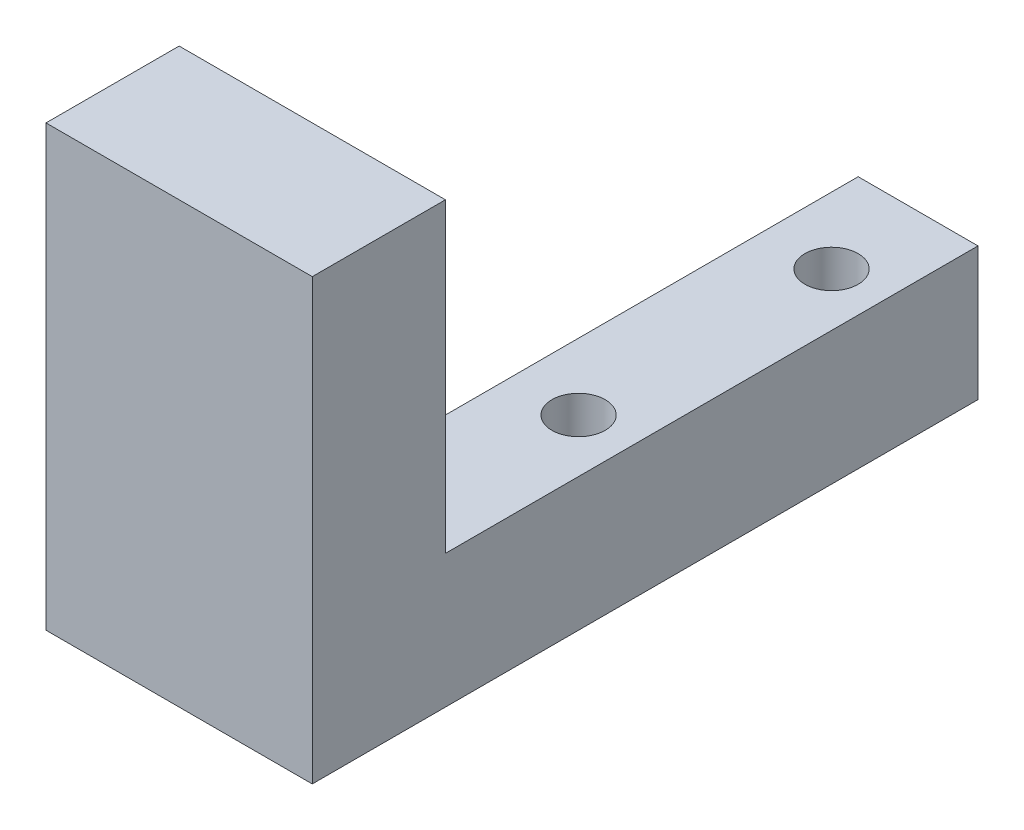
SolidWorks part; units mm, degrees
ref_plane "Front Plane" through (0, 0, 0) normal (0, 0, 1) x (1, 0, 0)
ref_plane "Top Plane" through (0, 0, 0) normal (0, 1, 0) x (1, 0, 0)
ref_plane "Right Plane" through (0, 0, 0) normal (1, 0, 0) x (0, 0, -1)
sketch "Sketch1" plane through (0, 0, 0) normal (0, 0, 1) x (1, 0, 0)
  line L1 (-7.8513, 3.6433) -> (2.1487, 3.6433)
  line L2 (-7.8513, 3.6433) -> (-7.8513, -6.3567)
  line L3 (-7.8513, -6.3567) -> (2.1487, -6.3567)
  line L4 (2.1487, 3.6433) -> (2.1487, -6.3567)
  dimension "D1" = 10
  dimension "D2" = 10
extrude "Boss-Extrude1" add sketch "Sketch1" along normal blind 50
sketch "Sketch3" plane through (-7.8513, 0, 0) normal (-1, 0, 0) x (0, 0, 1)
  line L0 (50, -6.3567) -> (0, -6.3567) construction
  line L1 (50, 3.6433) -> (40, 3.6433)
  line L2 (50, 3.6433) -> (50, -6.3567)
  line L3 (50, -6.3567) -> (40, -6.3567)
  line L4 (40, 3.6433) -> (40, -6.3567)
  dimension "D1" = 10
  dimension "D2" = 10
extrude "Boss-Extrude3" add sketch "Sketch3" along normal blind 11
sketch "Sketch8" plane through (0, 3.6433, 0) normal (0, 1, 0) x (1, 0, 0)
  line L1 (-18.8513, -50) -> (1.1487, -50)
  line L2 (-18.8513, -50) -> (-18.8513, -40)
  line L3 (-18.8513, -40) -> (1.1487, -40)
  line L4 (1.1487, -50) -> (1.1487, -40)
  dimension "D1" = 20
extrude "Boss-Extrude4" add sketch "Sketch8" along normal blind 23
sketch "Sketch9" plane through (0, 3.6433, 0) normal (0, 1, 0) x (1, 0, 0)
  line L0 (-2.8513, 0) -> (-2.8513, -5)
  line L3 (2.1487, 0) -> (-7.8513, 0) construction
  line L4 (-2.8513, -5) -> (-2.8513, -7)
  line L5 (-2.8513, -9) -> (-2.8513, -24)
  line L6 (-2.8513, -24) -> (-2.8513, -26)
  line L7 (2.1487, -50) -> (2.1487, 0) construction
  circle A0 centre (-2.8513, -7) radius 2
  circle A1 centre (-2.8513, -26) radius 2
  dimension "D1" = 5
  dimension "D3" = 15
  dimension "D2" = 2
  dimension "D4" = 2
extrude "Cut-Extrude2" cut sketch "Sketch9" against normal blind 23 contours A0
extrude "Cut-Extrude3" cut sketch "Sketch9<4>" against normal blind 23 contours A1
sketch "Sketch9<4>" plane through (0, 3.6433, 0) normal (0, 1, 0) x (1, 0, 0) same geometry as "Sketch9"
sketch "草图1" plane through (2.1487, 0, 0) normal (1, 0, 0) x (0, 0, -1)
  line L4 (0, -6.3567) -> (0, 3.6433)
  line L5 (0, 3.6433) -> (-50, 3.6433)
  line L6 (-50, 3.6433) -> (-50, -6.3567)
  line L7 (-50, -6.3567) -> (0, -6.3567)
  line L8 (0, -6.3567) -> (0, 3.6433)
  line L9 (0, 3.6433) -> (-50, 3.6433)
  line L10 (-50, 3.6433) -> (-50, -6.3567)
  line L11 (-50, -6.3567) -> (0, -6.3567)
  dimension "D1" = 0
extrude "切除-拉伸1" cut sketch "草图1" against normal up to surface (1 mm away) up to face at (1.1487, 18.0183, 46.25)
